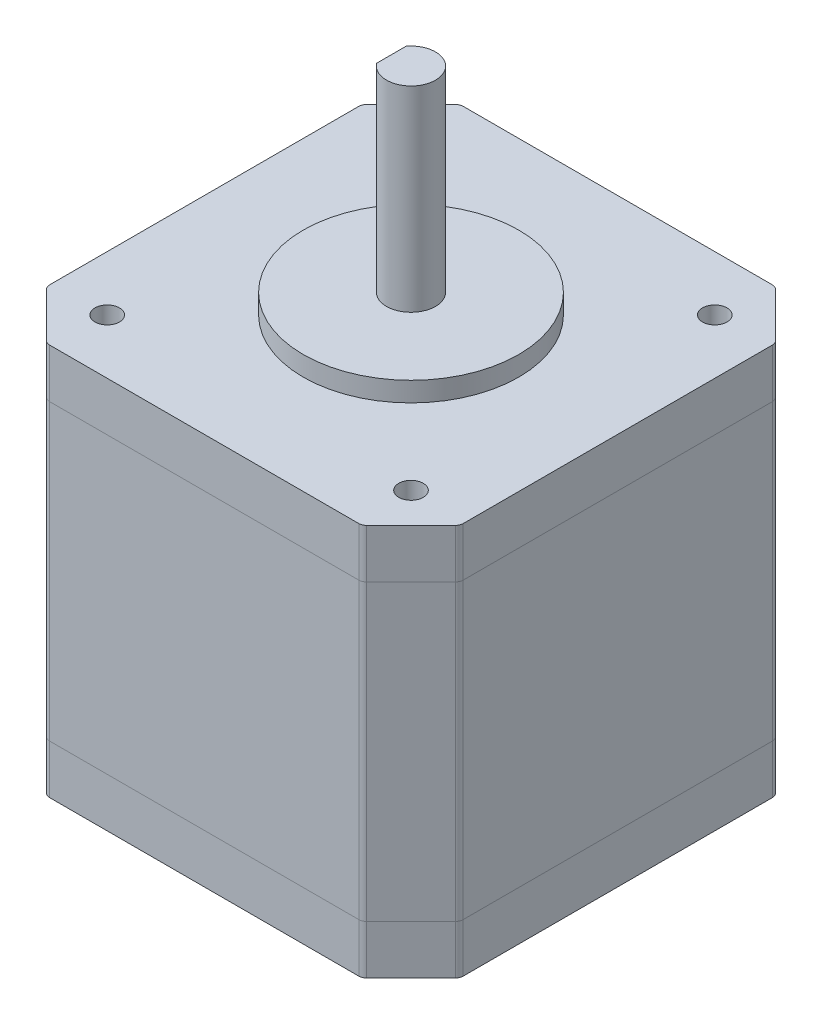
SolidWorks part; units mm, degrees
ref_plane "前视基准面" through (0, 0, 0) normal (0, 0, 1) x (1, 0, 0)
ref_plane "上视基准面" through (0, 0, 0) normal (0, 1, 0) x (1, 0, 0)
ref_plane "右视基准面" through (0, 0, 0) normal (1, 0, 0) x (0, 0, -1)
sketch "草图1" plane through (0, 0, 0) normal (0, 1, 0) x (1, 0, 0)
  line L0 (0, 74.4301) -> (0, -75.3699) construction
  line L1 (-87.211, 0) -> (85.3315, 0) construction
  line L2 (-15.7686, -21.1) -> (15.7686, -21.1)
  line L3 (-21.1, 15.7686) -> (-21.1, -15.7686)
  line L4 (-15.7686, 21.1) -> (15.7686, 21.1)
  line L5 (21.1, 15.7686) -> (21.1, -15.7686)
  line L6 (-15.5, 74.4301) -> (-15.5, -75.3699) construction
  line L7 (-87.211, -15.5) -> (85.3315, -15.5) construction
  line L8 (15.5, 74.4301) -> (15.5, -75.3699) construction
  line L9 (-87.211, 15.5) -> (85.3315, 15.5) construction
  line L10 (-87.211, 21.1) -> (85.3315, 21.1) construction
  line L11 (-21.1, 74.4301) -> (-21.1, -75.3699) construction
  line L12 (-20.8657, 16.3343) -> (-16.3343, 20.8657)
  line L13 (21.1, 74.4301) -> (21.1, -75.3699) construction
  line L14 (16.3343, 20.8657) -> (20.8657, 16.3343)
  line L15 (-87.211, -21.1) -> (85.3315, -21.1) construction
  line L16 (20.8657, -16.3343) -> (16.3343, -20.8657)
  line L17 (-20.8657, -16.3343) -> (-16.3343, -20.8657)
  line L21 (-2, 1.5) -> (-2, -1.5)
  circle A0 centre (-15.5, 15.5) radius 1.25
  circle A1 centre (15.5, 15.5) radius 1.25
  circle A2 centre (15.5, -15.5) radius 1.25
  circle A3 centre (-15.5, -15.5) radius 1.25
  circle A4 centre (0, 0) radius 11
  circle A5 centre (0, 0) radius 2.5
  arc A6 (-21.1, -15.7686) -> (-20.8657, -16.3343) centre (-20.3, -15.7686) ccw
  arc A7 (-16.3343, -20.8657) -> (-15.7686, -21.1) centre (-15.7686, -20.3) ccw
  arc A8 (15.7686, -21.1) -> (16.3343, -20.8657) centre (15.7686, -20.3) ccw
  arc A9 (20.8657, -16.3343) -> (21.1, -15.7686) centre (20.3, -15.7686) ccw
  arc A10 (21.1, 15.7686) -> (20.8657, 16.3343) centre (20.3, 15.7686) ccw
  arc A11 (16.3343, 20.8657) -> (15.7686, 21.1) centre (15.7686, 20.3) ccw
  arc A12 (-15.7686, 21.1) -> (-16.3343, 20.8657) centre (-15.7686, 20.3) ccw
  arc A13 (-20.8657, 16.3343) -> (-21.1, 15.7686) centre (-20.3, 15.7686) ccw
  point P23 (-21.1, 21.1)
  point P26 (21.1, 21.1)
  point P29 (21.1, -21.1)
  point P32 (-21.1, -21.1)
  point P47 (-21.1, -16.1)
  point P51 (-16.1, -21.1)
  point P54 (16.1, -21.1)
  point P57 (21.1, -16.1)
  point P60 (21.1, 16.1)
  point P63 (16.1, 21.1)
  point P66 (-16.1, 21.1)
  point P69 (-21.1, 16.1)
  dimension "D5" = 2.5
  dimension "D11" = 22
  dimension "D12" = 5
  dimension "D14" = 0.8
  dimension "D1" = 21.1
  dimension "D13" = 2
  dimension "D2" = 21.1
  dimension "D3" = 15.5
  dimension "D4" = 15.5
  dimension "D6" = 4
extrude "凸台-拉伸1" add sketch "草图1" along normal blind 40 contours L3 L17 L2 L16 L5 L14 L4 L12 A4 A3 A2 A1 A0 region at (-15.8464, 0, 20.4877)
extrude "切除-拉伸1" cut sketch "草图1<6>" along normal blind 35 contours L3 L17 L2 L16 L5 L14 L4 L12 A4 A3 A2 A1 A0 region at (-15.8464, 0, 20.4877)
sketch "草图1<6>" plane through (0, 0, 0) normal (0, 1, 0) x (1, 0, 0) same geometry as "草图1"
extrude "凸台-拉伸6" add sketch "草图1<7>" along normal blind 35 separate body contours L3 L17 L2 L16 L5 L14 L4 L12 A4 A3 A2 A1 A0 region at (-15.8464, 0, 20.4877)
sketch "草图1<7>" plane through (0, 0, 0) normal (0, 1, 0) x (1, 0, 0) same geometry as "草图1"
extrude "切除-拉伸2" cut sketch "草图1<8>" along normal blind 5 contours L3 L17 L2 L16 L5 L14 L4 L12 A4 A3 A2 A1 A0 region at (-15.8464, 0, 20.4877)
sketch "草图1<8>" plane through (0, 0, 0) normal (0, 1, 0) x (1, 0, 0) same geometry as "草图1"
extrude "凸台-拉伸7" add sketch "草图1<9>" along normal blind 5 separate body contours L3 L17 L2 L16 L5 L14 L4 L12 A4 A3 A2 A1 A0 region at (-15.8464, 0, 20.4877)
sketch "草图1<9>" plane through (0, 0, 0) normal (0, 1, 0) x (1, 0, 0) same geometry as "草图1"
extrude "凸台-拉伸2" add sketch "草图1<3>" along normal blind 42 contours A4 A5 region at (-10.6889, 0, 0)
sketch "草图1<3>" plane through (0, 0, 0) normal (0, 1, 0) x (1, 0, 0) same geometry as "草图1"
extrude "凸台-拉伸3" add sketch "草图1<4>" along normal blind 62 contours L21 A5 region at (0.1209, 0, 0)
sketch "草图1<4>" plane through (0, 0, 0) normal (0, 1, 0) x (1, 0, 0) same geometry as "草图1"
extrude "凸台-拉伸4" add sketch "草图1<5>" along normal blind 47 contours L21 A5 region at (-2.2018, 0, 0)
sketch "草图1<5>" plane through (0, 0, 0) normal (0, 1, 0) x (1, 0, 0) same geometry as "草图1"
sketch "草图2" plane through (0, 0, -21.1) normal (0, 0, -1) x (-1, 0, 0)
  line L0 (-15.7686, 0) -> (15.7686, 0)
  line L1 (-16.1, 6) -> (15.7686, 6)
  line L2 (0, 14.1622) -> (0, -8.6857)
  line L3 (-7, 14.1622) -> (-7, -8.6857)
  line L4 (7, 14.1622) -> (7, -8.6857)
  line L5 (-16.1, 0) -> (15.7686, 0) construction
  dimension "D1" = 6
  dimension "D2" = 7
  dimension "D3" = 7
extrude "凸台-拉伸5" add sketch "草图2" along normal blind 6 contours L4 L1 L2 L0 | L1 L3 L0 L2 region at (3.5, 3, -21.1) region at (-3.5, 3, -21.1)
fillet "圆角1" radius 1 8 edges at (0, 0, -27.1) (7, 3, -27.1) (0, 6, -27.1) (-7, 3, -27.1) (-7, 0, -24.1) (-7, 6, -24.1) (7, 0, -24.1) (7, 6, -24.1)
